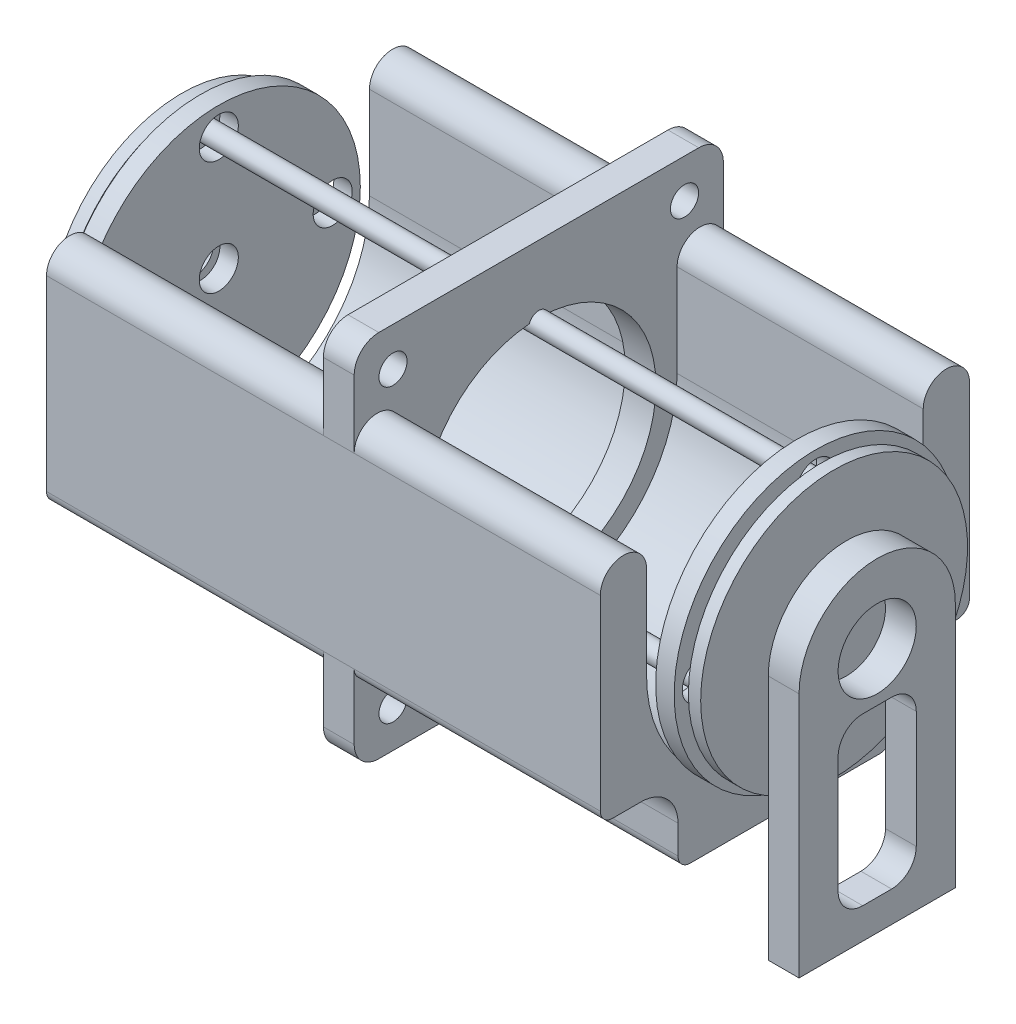
SolidWorks part; units mm, degrees
ref_plane "Front Plane" through (0, 0, 0) normal (0, 0, 1) x (1, 0, 0)
ref_plane "Top Plane" through (0, 0, 0) normal (0, 1, 0) x (1, 0, 0)
ref_plane "Right Plane" through (0, 0, 0) normal (1, 0, 0) x (0, 0, -1)
sketch "Sketch1" plane through (0, 0, 0) normal (1, 0, 0) x (0, 0, -1)
  line L1 (23.6855, -23.6855) -> (-23.6855, -23.6855) construction
  line L2 (23.6855, -23.6855) -> (23.6855, 23.6855) construction
  line L3 (23.6855, 23.6855) -> (-23.6855, 23.6855) construction
  line L4 (-23.6855, -23.6855) -> (-23.6855, 23.6855) construction
  line L5 (23.6855, -23.6855) -> (-23.6855, 23.6855) construction
  line L6 (23.6855, 23.6855) -> (-23.6855, -23.6855) construction
  line L7 (-30, 30) -> (30, 30)
  line L8 (-30, 30) -> (-30, -30)
  line L9 (-30, -30) -> (30, -30)
  line L10 (30, 30) -> (30, -30)
  line L11 (-30, 30) -> (30, -30) construction
  line L12 (-30, -30) -> (30, 30) construction
  circle A0 centre (-23.6855, 23.6855) radius 2.286
  circle A1 centre (23.6855, 23.6855) radius 2.286
  circle A2 centre (-23.6855, -23.6855) radius 2.286
  circle A3 centre (23.6855, -23.6855) radius 2.286
  circle A4 centre (0, 0) radius 19.05
  point P0 (0, 0)
  point P10 (0, 0)
  dimension "D1" = 38.1
  dimension "D2" = 60
  dimension "D5" = 60
extrude "Boss-Extrude1" add sketch "Sketch1" along normal blind 5
ref_plane "Plane1" through (-50, 0, 0) normal (1, 0, 0) x (0, 0, -1)
sketch "Sketch2" plane through (-50, 0, 0) normal (1, 0, 0) x (0, 0, -1)
  line L0 (0, 0) -> (0, 1.0694) construction
  circle A0 centre (0, 0) radius 3.175
  circle A1 centre (0, 18.5125) radius 1.5875 construction
  circle A2 centre (0, 18.5125) radius 3.175
  circle A3 centre (0, 0) radius 23
  circle A4 centre (-18.5125, 0) radius 1.5875 construction
  circle A5 centre (-18.5125, 0) radius 3.175
  circle A6 centre (0, -18.5125) radius 1.5875 construction
  circle A7 centre (0, -18.5125) radius 3.175
  circle A8 centre (18.5125, 0) radius 1.5875 construction
  circle A9 centre (18.5125, 0) radius 3.175
  dimension "D1" = 6.35
  dimension "D2" = 3.175
  dimension "D3" = 6.35
  dimension "D4" = 46
extrude "Boss-Extrude2" add sketch "Sketch2" along normal blind 3 separate body
ref_plane "Plane2" through (-45, 0, 0) normal (-1, 0, 0) x (0, 0, 1)
sketch "Sketch3" plane through (-45, 0, 0) normal (-1, 0, 0) x (0, 0, 1)
  line L0 (-22.4812, 0) -> (-22.4812, 15)
  line L1 (22.4812, 0) -> (22.4812, 15)
  line L2 (-23.371, -17.371) -> (-30, -17.371)
  line L3 (-30, 15) -> (-30, -17.371)
  line L4 (-17.371, -30) -> (17.371, -30)
  line L5 (-17.371, -23.371) -> (-17.371, -30)
  line L6 (17.371, -23.371) -> (17.371, -30)
  line L7 (23.371, -17.371) -> (30, -17.371)
  line L12 (30, -17.371) -> (30, 15)
  arc A0 (-22.4812, 0) -> (22.4812, 0) centre (0, 0) ccw
  arc A1 (-23.371, -17.371) -> (-17.371, -23.371) centre (-23.371, -23.371) cw
  arc A2 (17.371, -23.371) -> (23.371, -17.371) centre (23.371, -23.371) cw
  arc A3 (-30, 15) -> (-22.4812, 15) centre (-26.2406, 15) cw
  arc A4 (30, 15) -> (22.4812, 15) centre (26.2406, 15) ccw
  dimension "D1" = 6
  dimension "D2" = 6
extrude "Boss-Extrude3" add sketch "Sketch3" against normal blind 90 separate body
fillet "Fillet1" radius 2 4 edges at (0, -30, 17.371) (0, -30, -17.371) (0, -17.371, -30) (0, -17.371, 30)
fillet "Fillet3" radius 4 4 edges at (2.5, 30, -30) (2.5, -30, -30) (2.5, -30, 30) (2.5, 30, 30)
ref_plane "Plane9" through (-53, 0, 0) normal (-1, 0, 0) x (0, 0, 1)
sketch "Sketch16" plane through (-53, 0, 0) normal (-1, 0, 0) x (0, 0, 1)
  circle A0 centre (0, 0) radius 21.6875
  circle A1 centre (0, 0) radius 3.175
  dimension "D1" = 6.35
extrude "Boss-Extrude7" add sketch "Sketch16" against normal blind 2 separate body
sketch "Sketch21" plane through (0, 0, 0) normal (1, 0, 0) x (0, 0, -1)
  circle A0 centre (-18.5125, 0) radius 1.5875
  circle A1 centre (0, 18.5125) radius 1.5875
  circle A2 centre (18.5125, 0) radius 1.5875
  circle A3 centre (0, -18.5125) radius 1.5875
  dimension "D1" = 4
extrude "Boss-Extrude11" add sketch "Sketch21" along normal mid plane 101.6 separate body
ref_axis "Axis1" through (-65.54, 0, 0) along (1, 0, 0)
mirror "Mirror2" about plane through (0, 0, 0) normal (1, 0, 0) of bodies 102 113
ref_plane "Plane12" through (55, 0, 0) normal (1, 0, 0) x (0, 0, -1)
sketch "Sketch22" plane through (55, 0, 0) normal (1, 0, 0) x (0, 0, -1)
  line L0 (-12.7, 0) -> (-12.7, -40)
  line L1 (12.7, 0) -> (12.7, -40)
  line L3 (12.7, -40) -> (-12.7, -40)
  line L4 (-12.7, -40) -> (-12.5635, -39.8925)
  line L5 (-6.35, -12) -> (-6.35, -31)
  line L6 (6.35, -12) -> (6.35, -31)
  line L7 (-2.35, -8) -> (2.35, -8)
  line L9 (-2.35, -35) -> (2.35, -35)
  circle A0 centre (0, 0) radius 6.35
  arc A1 (-12.7, 0) -> (12.7, 0) centre (0, 0) cw
  arc A2 (-6.35, -31) -> (-2.35, -35) centre (-2.35, -31) ccw
  arc A3 (2.35, -35) -> (6.35, -31) centre (2.35, -31) ccw
  arc A4 (6.35, -12) -> (2.35, -8) centre (2.35, -12) ccw
  arc A5 (-6.35, -12) -> (-2.35, -8) centre (-2.35, -12) cw
  dimension "D1" = 4
  dimension "D3" = 12.7
  dimension "D2" = 25.4
  dimension "D4" = 19
extrude "Boss-Extrude12" add sketch "Sketch22" along normal blind 5 separate body contours A1 L0 L3 L1 A0 L5 A5 L7 A4 L6 A3 L9 A2 region at (55, 12.115, 0)
